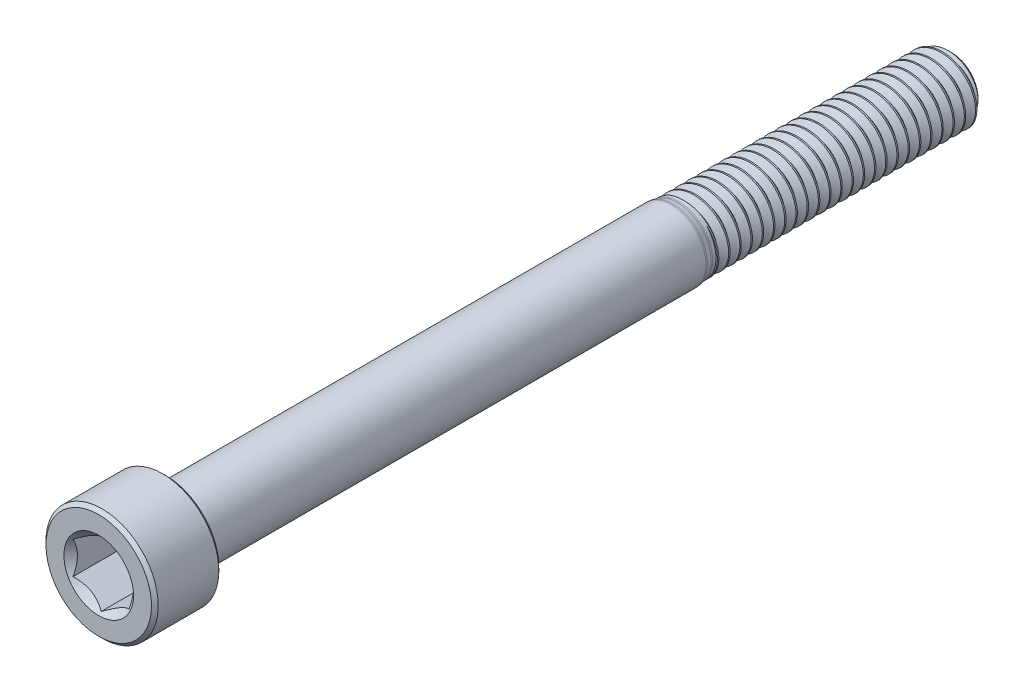
SolidWorks part; units mm, degrees
ref_plane "Front Plane" through (0, 0, 0) normal (0, 0, 1) x (1, 0, 0)
ref_plane "Top Plane" through (0, 0, 0) normal (0, 1, 0) x (1, 0, 0)
ref_plane "Right Plane" through (0, 0, 0) normal (1, 0, 0) x (0, 0, -1)
sketch "Sketch1" plane through (0, 0, 0) normal (1, 0, 0) x (0, 0, -1)
  line L0 (-38, 0) -> (38, 0) construction
  line L1 (38, 0) -> (38, 2.3505) construction
  line L2 (38, 2.3505) -> (37.3505, 3) construction
  line L3 (37.3505, 3) -> (37.25, 3) construction
  line L4 (37.25, 3) -> (-32, 3) construction
  line L5 (-32, 3) -> (-32, 5) construction
  line L6 (-32, 5) -> (-38, 5) construction
  line L7 (-38, 5) -> (-38, 0) construction
  line L8 (38, 2.3505) -> (38, 3) construction
  line L9 (37.9375, 3.1083) -> (38.4375, 2.2422) construction
  line L10 (38.4375, 2.2422) -> (38.9375, 3.1083) construction
  line L11 (38.9375, 3.1083) -> (37.9375, 3.1083) construction
  line L12 (38.4375, 3.1083) -> (38.4375, 3) construction
  line L13 (38.4375, 2.2422) -> (38.4375, 2.3505) construction
  line L14 (38.375, 2.3505) -> (38.5, 2.3505) construction
  line L15 (38, 3) -> (38.875, 3) construction
  line L16 (37.9688, 3.0541) -> (38.9062, 3.0541) construction
  line L17 (38, 0) -> (38, -3) construction
  line L18 (-32.3, 5) -> (-32, 4.7) construction
  line L19 (-37.7, 5) -> (-38, 4.7) construction
  line L20 (-32, 3) -> (-32, 0) construction
  line L21 (-32, 1.5) -> (-8.6667, 1.5) construction
  line L22 (-8.6667, 1.5) -> (14.6667, 1.5) construction
  line L23 (14.6667, 1.5) -> (38, 1.5) construction
  line L24 (-8.6667, 1.5) -> (-8.6667, 3) construction
  line L25 (-8.6667, 3) -> (-8.6667, 5) construction
  line L26 (14.6667, 1.5) -> (14.6667, 5) construction
  point P0 (-38, 2.5)
  point P3 (35.5, 3)
  point P4 (0, 0)
  point P18 (14.6667, 3)
  point P22 (38.4375, 2.3505)
  point P24 (37.25, 3)
  point P25 (38.4375, 3)
  point P28 (38.4375, 3.0541)
  point P29 (35.5, -3)
  point P30 (-8.6667, 3)
  point P31 (-35, 5)
  point P37 (-33.05, 5)
  point P38 (-37.55, 5)
  point P45 (-8.6667, 1.5)
  point P46 (14.6667, 1.5)
  point P49 (14, 3)
  dimension "D1" = 45
  dimension "D2" = 0.125
  dimension "D7" = 0.3
  dimension "D8" = 0.3
  dimension "D9" = 0.3
  dimension "D10" = 0.15
  dimension "D11" = 0.75
  dimension "Drive Size" = 5
  dimension "Head Diameter" = 10
  dimension "Head Height" = 6
  dimension "Thread Pitch" = 1
  dimension "Thread Dia" = 6
  dimension "Length" = 70
  dimension "D12" = 0.75
  dimension "D4" = 2.5
  dimension "Minimum Thread Length" = 24
  dimension "D3" = 46
sketch "Sketch2" plane through (0, 0, 0) normal (1, 0, 0) x (0, 0, -1)
  line L0 (-38, 0) -> (-38, 4.7)
  line L1 (-37.7, 5) -> (-32.3, 5)
  line L2 (-32, 4.7) -> (-32, 3.4083)
  line L4 (37.3505, 3) -> (38, 2.3505)
  line L5 (38, 2.3505) -> (38, 0)
  line L6 (-32, 5) -> (-38, 5) construction
  line L7 (38, 0) -> (-38, 0)
  line L8 (-37.7, 5) -> (-38, 4.7) construction
  line L10 (-37.7, 5) -> (-38, 4.7)
  line L14 (-32.3, 5) -> (-32, 4.7) construction
  line L16 (-32.3, 5) -> (-32, 4.7)
  line L17 (-32, 3) -> (-32, 5) construction
  line L18 (-31.7, 3.1083) -> (13.0069, 3.1083)
  line L19 (13.6989, 3) -> (37.3505, 3)
  line L20 (37.25, 3) -> (-32, 3) construction
  line L21 (13.1532, 3.0938) -> (13.5526, 3.0144)
  line L22 (38.9375, 3.1083) -> (37.9375, 3.1083) construction
  arc A1 (-32, 3.4083) -> (-31.7, 3.1083) centre (-31.7, 3.4083) ccw
  arc A2 (13.0069, 3.1083) -> (13.1532, 3.0938) centre (13.0069, 2.3583) cw
  arc A3 (13.5526, 3.0144) -> (13.6989, 3) centre (13.6989, 3.75) ccw
  point P39 (13.625, 3)
  dimension "D3" = 0.3
  dimension "D6" = 0.75
  dimension "D4" = 11.25
  dimension "D5" = 0.375
revolve "Revolve1" add sketch "Sketch2" angle 360 about L7
sketch "Sketch3" plane through (0, 0, 38) normal (0, 0, 1) x (1, 0, 0)
  line L1 (2.5, -1.4434) -> (2.5, 1.4434)
  line L2 (2.5, 1.4434) -> (0, 2.8868)
  line L3 (0, 2.8868) -> (-2.5, 1.4434)
  line L4 (-2.5, 1.4434) -> (-2.5, -1.4434)
  line L5 (-2.5, -1.4434) -> (0, -2.8868)
  line L6 (0, -2.8868) -> (2.5, -1.4434)
  circle A0 centre (0, 0) radius 2.5 construction
  circle A1 centre (0, 0) radius 5 construction
  circle A2 centre (0, 0) radius 5 construction
  circle A3 centre (0, 0) radius 2.8868 construction
  dimension "D1" = 5.7735
extrude "Cut-Extrude1" cut sketch "Sketch3" against normal offset from surface (5 mm away) 1 up to face at (0, 4.7, 32)
sketch "Sketch4" plane through (0, 0, 38) normal (0, 0, 1) x (1, 0, 0)
  circle A0 centre (0, 0) radius 3.1033
  dimension "D1" = 6.2065
extrude "Cut-Extrude2" cut sketch "Sketch4" against normal up to vertex (3 mm away) draft 45 up to point (0, 5, 35)
sketch "Sketch11" plane through (0, 0, 0) normal (1, 0, 0) x (0, 0, -1)
  line L0 (-38, 0) -> (38, 0) construction
  line L1 (-38, 0) -> (38, 0) construction
  line L2 (-27.975, 0) -> (-27.975, 3) construction
  line L3 (37.25, 3) -> (-32, 3) construction
  line L4 (8.9819, 0) -> (8.9819, 3) construction
  point P2 (-27.975, 0)
  point P3 (8.9819, 0)
  dimension "D1" = 4.025
  dimension "D2" = 4.025
sketch "Sketch6" plane through (0, 0, -38) normal (0, 0, -1) x (-1, 0, 0)
  circle A0 centre (0, 0) radius 3
curve "Helix/Spiral1" pitch 1 height 25 radius 3 centre (0, 0, -38) axis (0, 0, 1) start towards (0, 1, 0)
sketch "Sketch10" plane through (0, 0, 0) normal (1, 0, 0) x (0, 0, -1)
  line L0 (14, -3) -> (14, 3)
  line L2 (-38, 0) -> (38, 0) construction
  point P3 (14, 0)
split "Split1" trim tools "Sketch10" bodies to split 106 resulting bodies 114 115
sketch "Sketch7" plane through (0, 0, 0) normal (1, 0, 0) x (0, 0, -1)
  line L0 (37.9688, 3.0541) -> (38.9062, 3.0541)
  line L1 (38.9062, 3.0541) -> (38.5, 2.3505)
  line L2 (38.5, 2.3505) -> (38.375, 2.3505)
  line L3 (38.375, 2.3505) -> (37.9688, 3.0541)
sweep "Cut-Sweep1" cut profiles "Sketch7" path "Helix/Spiral1" align with end faces yes
sketch "Sketch8" plane through (0, 0, 0) normal (1, 0, 0) x (0, 0, -1)
  line L0 (-32, 0) -> (-32, 3)
  line L2 (-32, 3) -> (14, 3)
  line L4 (14, 3) -> (15.7321, 0)
  line L5 (15.7321, 0) -> (-32, 0)
  line L6 (37.25, 3) -> (-32, 3) construction
  line L7 (-38, 0) -> (38, 0) construction
  dimension "D1" = 60
  dimension "D2" = 24
revolve "Revolve2" add sketch "Sketch8" angle 360 about L5
equation "\"D2@Sketch1\" = \"Thread Pitch@Sketch1\" / 8"
equation "\"D4@Helix/Spiral1\" = \"Thread Pitch@Sketch1\""
equation "\"D7@Sketch1\" = \"Head Height@Sketch1\" * .05"
equation "\"D8@Sketch1\"=\"D7@Sketch1\""
equation "\"D9@Sketch1\"=\"D7@Sketch1\""
equation "\"D10@Sketch1\"=\"D7@Sketch1\"/2"
equation "\"D11@Sketch1\"=\"D10@Sketch1\"*5"
equation "\"D4@Sketch1\"=\"Thread Pitch@Sketch1\"*2.5"
equation "\"D12@Sketch1\"=\"Thread Pitch@Sketch1\"*.75"
equation "\"D3@Helix/Spiral1\"=\"Minimum Thread Length@Sketch1\"+\"Thread Pitch@Sketch1\""
equation "\"D2@Sketch8\"=\"Minimum Thread Length@Sketch1\""
equation "\"D3@Sketch2\"=\"Thread Dia@Sketch1\"*0.05"
equation "\"D5@Sketch2\"=\"D12@Sketch1\"*0.5"
equation "\"D6@Sketch2\"=\"Thread Dia@Sketch1\"*0.125"
equation "\"D1@Sketch11\"=\"D3@Sketch1\"*0.0875"
equation "\"D2@Sketch11\"=\"D1@Sketch11\""
equation "\"D1@Sketch4\"=\"D1@Sketch3\"*1.075"
